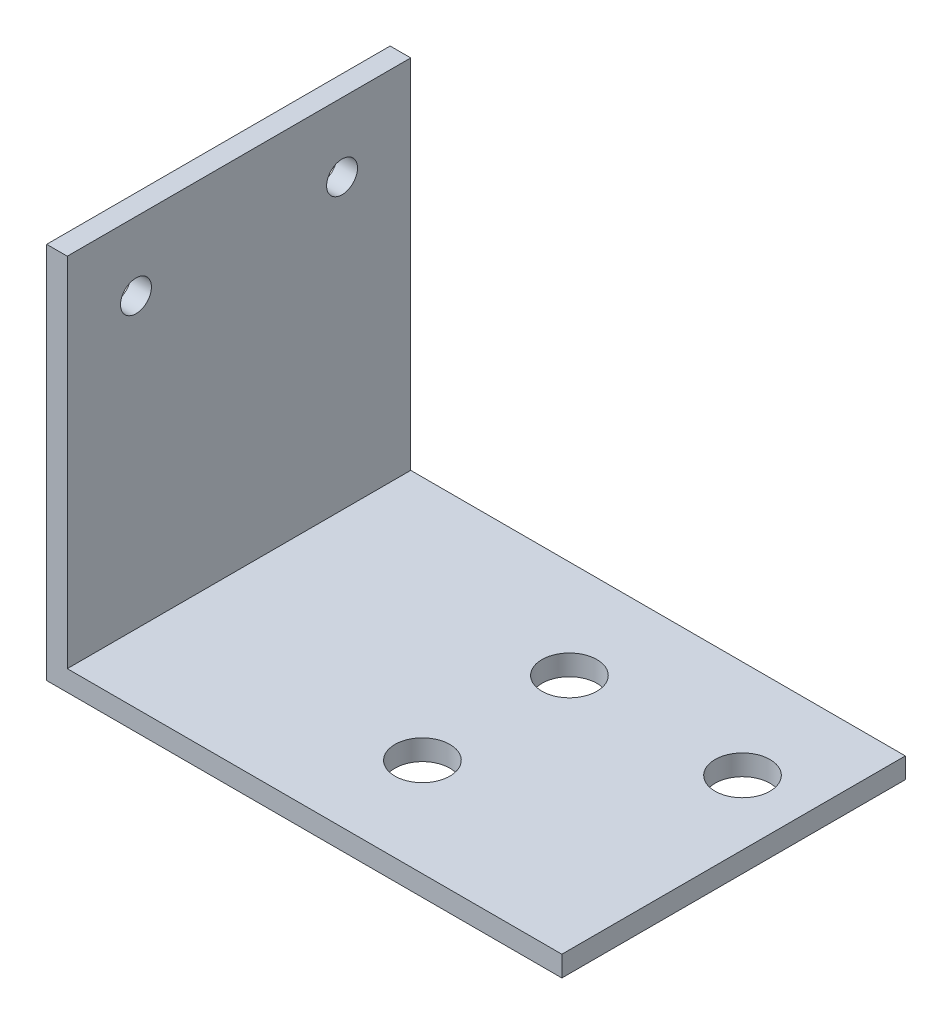
SolidWorks part; units mm, degrees
material "PBT Общее назначение"
ref_plane "Спереди" through (0, 0, 0) normal (0, 0, 1) x (1, 0, 0)
ref_plane "Сверху" through (0, 0, 0) normal (0, 1, 0) x (1, 0, 0)
ref_plane "Справа" through (0, 0, 0) normal (1, 0, 0) x (0, 0, -1)
sketch "Эскиз1" plane through (0, 0, 0) normal (0, 0, 1) x (1, 0, 0)
  line L0 (0, 0) -> (75, 0)
  line L1 (75, 0) -> (75, 3)
  line L2 (75, 3) -> (3, 3)
  line L3 (3, 3) -> (3, 55)
  line L4 (3, 55) -> (0, 55)
  line L5 (0, 55) -> (0, 0)
  dimension "D1" = 3
  dimension "D2" = 3
  dimension "D3" = 75
  dimension "D4" = 55
extrude "Бобышка-Вытянуть1" add sketch "Эскиз1" along normal blind 50
sketch "Эскиз2" plane through (0, 0, 0) normal (-1, 0, 0) x (0, 0, 1)
  line L0 (25, 55) -> (25, 0) construction
  line L1 (50, 55) -> (0, 55) construction
  line L2 (50, 0) -> (0, 0) construction
sketch "Эскиз3" plane through (0, 3, 0) normal (0, 1, 0) x (1, 0, 0)
  line L4 (67.25, -40) -> (67.25, -39)
  line L5 (67.25, -39) -> (39.25, -39)
  line L6 (39.25, -39) -> (39.25, -40)
  line L7 (39.25, -40) -> (67.25, -40)
  line L8 (67.25, -40) -> (67.25, -39)
  line L9 (67.25, -39) -> (39.25, -39)
  line L10 (39.25, -39) -> (39.25, -40)
  line L11 (39.25, -40) -> (67.25, -40)
  line L12 (67.25, -10) -> (39.25, -10)
  line L13 (67.25, -11) -> (67.25, -10)
  line L14 (39.25, -11) -> (67.25, -11)
  line L15 (39.25, -10) -> (39.25, -11)
  line L16 (67.25, -10) -> (39.25, -10)
  line L17 (67.25, -11) -> (67.25, -10)
  line L18 (39.25, -11) -> (67.25, -11)
  line L19 (39.25, -10) -> (39.25, -11)
  circle A0 centre (23, 25) radius 1.55 construction
  circle A1 centre (40.4, -35.7) radius 2
  circle A2 centre (40.4, -35.7) radius 2
  circle A3 centre (40.4, -14.3) radius 2
  circle A4 centre (40.4, -14.3) radius 2
  circle A7 centre (53.25, -32) radius 1
  circle A8 centre (53.25, -32) radius 1
  circle A9 centre (53.25, -18) radius 1
  circle A10 centre (53.25, -18) radius 1
  circle A11 centre (23, 25) radius 1.55
  circle A12 centre (23, -70) radius 1.55 construction
  circle A13 centre (23, -70) radius 1.55
  dimension "D1" = 0
  dimension "D2" = 0
  dimension "D4" = 0
  dimension "D5" = 0
  dimension "D6" = 0
  dimension "D7" = 0
sketch "Эскиз6" plane through (0, 3, 0) normal (0, 1, 0) x (1, 0, 0)
  circle A5 centre (40.4, -14.3) radius 2
  circle A6 centre (40.4, -14.3) radius 2
  circle A7 centre (40.4, -35.7) radius 2
  circle A8 centre (40.4, -35.7) radius 2
  dimension "D3" = 0
  dimension "D4" = 0
extrude "Вырез-Вытянуть2" cut sketch "Эскиз6" against normal through all
sketch "Sketch1" plane through (0, 3, 0) normal (0, 1, 0) x (1, 0, 0)
  circle A0 centre (65.6, -14.3) radius 2 construction
  circle A1 centre (65.6, -14.3) radius 2
extrude "Cut-Extrude1" cut sketch "Sketch1" against normal through all
sketch "Sketch2" plane through (0, 3, 0) normal (0, 1, 0) x (1, 0, 0)
  circle A0 centre (40.4, -14.3) radius 4
  circle A1 centre (65.6, -14.3) radius 4
  circle A2 centre (40.4, -35.7) radius 4
  dimension "D1" = 8
  dimension "D2" = 8
  dimension "D3" = 8
extrude "Cut-Extrude2" cut sketch "Sketch2" against normal through all
sketch "Sketch3" plane through (0, 3, 0) normal (0, 1, 0) x (1, 0, 0)
  line L0 (65.6, -14.3) -> (40.4, -14.3) construction
  line L1 (40.4, -14.3) -> (40.4, -35.7) construction
ref_plane "Отв вдоль" through (0, 0, 14.3) normal (0, 0, -1) x (-1, 0, 0)
ref_plane "Отв поп" through (40.4, 0, 0) normal (-1, 0, 0) x (0, 0, 1)
sketch "Sketch4" plane through (0, 0, 0) normal (-1, 0, 0) x (0, 0, 1)
  line L0 (0, 45) -> (50, 45) construction
  line L1 (0, 55) -> (0, 0) construction
  line L2 (50, 55) -> (50, 0) construction
  line L3 (50, 55) -> (0, 55) construction
  circle A0 centre (10, 45) radius 2.25
  circle A1 centre (40, 45) radius 2.25
  dimension "D2" = 4.5
  dimension "D3" = 4.5
  dimension "D4" = 10
  dimension "D5" = 10
  dimension "D1" = 10
extrude "Cut-Extrude3" cut sketch "Sketch4" against normal through all
